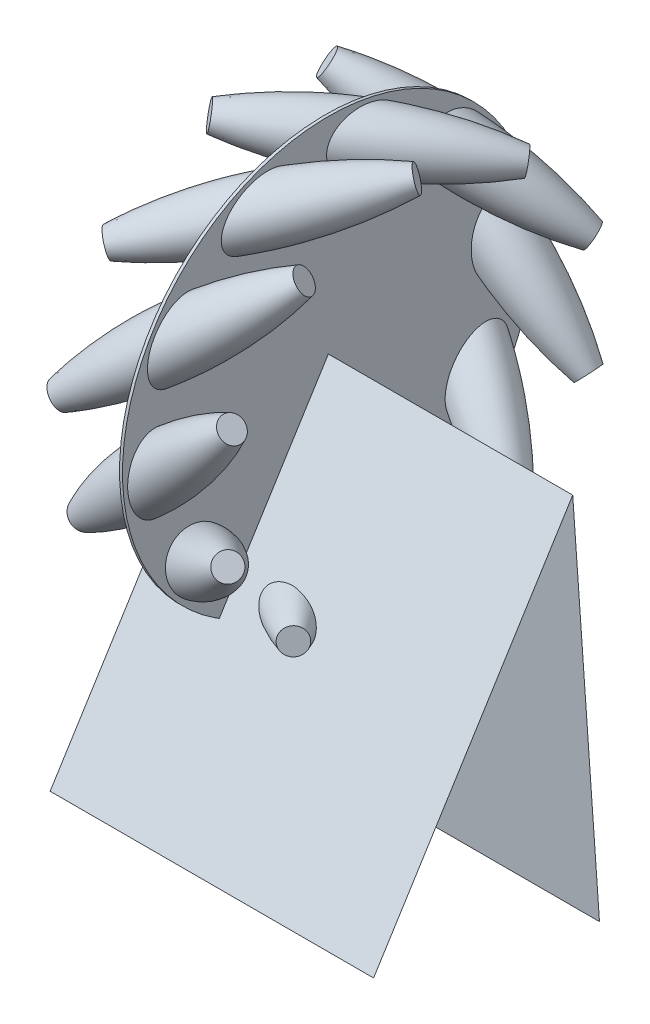
SolidWorks part; units mm, degrees
note: '?' marks a value the reader was unsure of.
ref_plane "前视基准面" through (0, 0, 0) normal (0, 0, 1) x (1, 0, 0)
ref_plane "上视基准面" through (0, 0, 0) normal (0, 1, 0) x (1, 0, 0)
ref_plane "右视基准面" through (0, 0, 0) normal (1, 0, 0) x (0, 0, -1)
sketch "草图1" plane through (0, 0, 0) normal (1, 0, 0) x (0, 0, -1)
  line L0 (0, 0) -> (0, 70) construction
  line L1 (0, 0) -> (35, 60.6218) construction
  line L2 (0, 0) -> (60.6218, 35) construction
  line L3 (0, 0) -> (70, 0) construction
  line L4 (0, 0) -> (60.6218, -35) construction
  line L5 (0, 0) -> (35, -60.6218) construction
  line L6 (0, 0) -> (0, -70) construction
  line L7 (0, 0) -> (-35, -60.6218) construction
  line L8 (0, 0) -> (-60.6218, -35) construction
  line L9 (0, 0) -> (-70, 0) construction
  line L10 (0, 0) -> (-60.6218, 35) construction
  line L11 (0, 0) -> (-35, 60.6218) construction
  line L12 (0, 0) -> (65.7785, -23.9414) construction
  line L13 (56.2917, 32.5) -> (60.6218, -22.0645)
  circle A0 centre (0, 0) radius 65
  circle A1 centre (0, 0) radius 70
  point P18 (0, 0)
  dimension "D1" = 12
  dimension "D2" = 50
ref_plane "基准面1" through (0, 4.6426, -58.5024) normal (0, -0.0791, 0.9969) x (0, -0.9969, -0.0791)
sketch "草图2" plane through (0, 4.6426, -58.5024) normal (0, -0.0791, 0.9969) x (0, -0.9969, -0.0791)
  line L0 (26.7911, 0) -> (26.7911, 54.7361) construction
  line L1 (26.7911, 54.7361) -> (-27.945, 0)
  dimension "D1" = 45
ref_axis "基准轴1" through (0, 0, 0) along (1, 0, 0)
sketch3d "3D草图1"
  line L0 (0, 0, 0) -> (101.2389, 0, 0) construction
  line L1 (27.368, 5.2177, -58.4567) -> (26.3985, 0, 0) construction
  line L2 (54.7361, -22.0645, -60.6218) -> (0, 32.5, -56.2917) construction
ref_plane "基准面5" through (13.1947, 13.1258, 1.3904) normal (0.707, 0.7033, 0.0745) x (0.0528, 0.0525, -0.9972)
sketch3d "3D草图3"
  line L1 (0, 0, 70) -> (19.022, 0, 70) construction
  line L3 (0, 0, -70) -> (33.775, 0, -70) construction
  point P0 (0, 0, 70)
sketch "特征线" plane through (13.1947, 13.1258, 1.3904) normal (0.707, 0.7033, 0.0745) x (0.0528, 0.0525, -0.9972)
  line L3 (60.0139, -15.6023) -> (1.3943, -18.6176) construction
  ellipse E0 centre (1.3943, -18.6176) end of major axis (6.479, -117.4669) minor radius 68.5
  dimension "D1" = 137
  dimension "D2" = 197.96
sketch "草图5" plane through (13.1947, 13.1258, 1.3904) normal (0.707, 0.7033, 0.0745) x (0.0528, 0.0525, -0.9972)
  line L0 (62.185, -54.2456) -> (57.8428, 23.041) construction
  line L1 (62.185, -54.2456) -> (57.8428, 23.041)
  line L2 (57.8428, 23.041) -> (62.3614, 23.2949)
  line L3 (62.185, -54.2456) -> (66.3501, -54.0116)
  ellipse E0 centre (1.3943, -18.6176) end of major axis (6.479, -117.4669) minor radius 68.5 construction
  ellipse E1 centre (1.3943, -18.6176) end of major axis (6.479, -117.4669) minor radius 68.5 (66.3501, -54.0116) -> (62.3614, 23.2949) ccw
revolve "旋转1" add sketch "草图5" angle 360 about L1
ref_plane "基准面6" through (26.3985, 0, 0) normal (1, 0, 0) x (0, 0, -1)
sketch "草图6" plane through (26.3985, 0, 0) normal (1, 0, 0) x (0, 0, -1)
  circle A0 centre (0, 0) radius 70 construction
  circle A1 centre (0, 0) radius 70
extrude "凸台-拉伸1" add sketch "草图6" along normal mid plane 1
pattern_circular "阵列(圆周)2" count 10 over 360 about axis through (0, 0, 0) along (1, 0, 0) of "旋转1"
other "Configuration Table"
sketch "草图7" plane through (0, 0, 0) normal (0, 0, 1) x (1, 0, 0)
  line L0 (67.1878, 30.2938) -> (61.1961, 17.876)
  line L2 (61.1961, 17.876) -> (54.1338, 17.876)
  line L3 (67.1878, 30.2938) -> (67.1878, 42.7765)
  line L4 (67.1878, 42.7765) -> (61.7777, 62.7388)
sketch "草图8" plane through (0, 0, 0) normal (1, 0, 0) x (0, 0, -1)
  line L0 (0, 0) -> (-67.7114, -108.3608)
  line L1 (0, 0) -> (9.1025, -130.1715)
  line L2 (0, 0) -> (0, -143.1755) construction
  line L3 (0, 46.9609) -> (0, -46.9609) construction
  dimension "D1" = 32
  dimension "D2" = 36
surface "曲面-拉伸1" sketch "草图8" parameters "D1"=110
surface "曲面-旋转1" sketch "草图7" parameters "D1"=360
surface "曲面-剪裁1"
sketch "草图9" plane through (0, 0, 0) normal (1, 0, 0) x (0, 0, -1)
sketch "草图10" plane through (0, 0, 0) normal (1, 0, 0) x (0, 0, -1)
  line L0 (4.3764, -62.586) -> (-26.2451, -42.001)
  line L1 (-22.6681, -36.2765) -> (-33.2465, -53.2055) construction
surface "曲面-剪裁2"
sketch "草图11" plane through (0, 0, 0) normal (0, -0.5299, -0.848) x (-1, 0, 0)
  line L0 (-65.3584, -49.5266) -> (-63.5365, -56.2493)
  line L1 (-67.1878, -42.7765) -> (-65.3584, -49.5266) construction
sketch3d "3D草图4"
  line L0 (63.5365, -47.7021, 29.8076) -> (63.5365, -77.1863, -17.3769) construction
  line L1 (63.5365, -55.4008, 17.4871) -> (63.5365, -39.8243, 42.4147) construction
  line L3 (61.7775, -62.5865, -4.3765) -> (67.1878, -42.6723, -2.9839) construction
  spline S0 degree 3 poles (63.5365, -47.7021, 29.8076) (63.5365, -54.1923, 19.4211) (58.7395, -66.0826, 10.8621) (56.9461, -66.1414, -0.8137) knots 0 0 0 0 1 1 1 1
  spline S1 degree 3 poles (61.7777, -62.586, -4.3764) (61.3381, -65.0135, 0.0545) (57.1652, -64.7494, -1.2293) (56.9461, -66.1414, -0.8137) knots 0 0 0 0 1 1 1 1
  spline S2 degree 3 poles (65.3584, -42.0009, 26.2451) (65.3536, -42.2988, 25.8019) (65.3393, -42.8951, 24.915) (65.2976, -43.9396, 23.3614) (65.2271, -45.1382, 21.5781) (65.0791, -46.9382, 18.9008) (64.8188, -49.1854, 15.5577) (64.3959, -51.8656, 11.5709) (63.8703, -54.5502, 7.5768) (63.3791, -56.6855, 4.4009) (62.9764, -58.2883, 2.0166) (62.6989, -59.3451, 0.4446) (62.4065, -60.4141, -1.1456) (62.1087, -61.4646, -2.7082) (61.8902, -62.2091, -3.8159) (61.7775, -62.5865, -4.3771) knots 0 0 0 0 0.043119 0.086313 0.151515 0.216916 0.347383 0.477798 0.606745 0.738719 0.789693 0.841267 0.893485 0.946384 1 1 1 1 construction
ref_axis "基准轴2" through (63.5365, -47.7021, 29.8076) along (0, -0.5299, -0.848)?
sketch "草图12" plane through (40.7636, -15.6241, 37.6505) normal (0.7071, -0.271, 0.6531) x (0.6098, -0.2337, -0.7573)
  line L0 (50.9174, -40.6125) -> (42.5741, -40.6125) construction
  line L1 (46.7457, -36.4409) -> (46.7457, -44.7842) construction
  circle A0 centre (46.7457, -40.6125) radius 4.1716 construction
  point P6 (46.7457, -40.6125)
ref_axis "基准轴3" through (-33.6532, -30.5947, -79.3875) along (0.7071, -0.271, 0.6531)?
sketch "草图14" plane through (40.7636, -15.6241, 37.6505) normal (0.7071, -0.271, 0.6531) x (0.6098, -0.2337, -0.7573)
  line L0 (46.7457, -40.6125) -> (50.5684, -38.9424) construction
  circle A0 centre (46.7457, -40.6125) radius 4.1716 construction
ref_plane "基准面7" through (-4.6874, -53.0917, -16.9569) normal (-0.0838, -0.9492, -0.3032) x (-0.9965, 0.0798, 0.0255)
sketch "草图15" plane through (-4.6874, -53.0917, -16.9569) normal (-0.0838, -0.9492, -0.3032) x (-0.9965, 0.0798, 0.0255)
  line L1 (3.3059, 47.0219) -> (29.4391, 47.0219)
  line L2 (3.3059, 47.0219) -> (3.3059, -2.1925)
  line L3 (3.3059, -2.1925) -> (29.4391, -2.1925)
  line L4 (29.4391, 47.0219) -> (29.4391, -2.1925)
surface "曲面-基准面1" sketch "草图15"
sketch3d "3D草图6"
  spline S0 degree 3 poles (26.8985, -49.734, -36.2009) (39.5069, -54.09, -26.048) (49.9831, -58.8819, -13.9404) (57.6651, -63.8071, -0.6434) knots 0 0 0 0 1 1 1 1 weights 1 0.978937 0.978937 1 only from (25.8631, -52.6021, -36.3032) to (56.9461, -66.1414, -0.8137)
  spline S1 degree 3 poles (51.8071, -65.139, 5.1463) (43.0575, -63.0086, 0.8945) (34.6863, -60.5671, -4.4356) (26.8985, -57.8744, -10.7135) knots 0 0 0 0 1 1 1 1 weights 1 0.991836 0.991836 1
  spline S2 degree 3 poles (51.8071, -65.139, 5.1463) (43.0575, -63.0086, 0.8945) (34.6863, -60.5671, -4.4356) (26.8985, -57.8744, -10.7135) knots 0 0 0 0 1 1 1 1 weights 1 0.991836 0.991836 1
  spline S3 degree 3 poles (25.8631, -52.6021, -36.3032) (38.5646, -56.7725, -26.1884) (49.1485, -61.3827, -14.1041) (56.9461, -66.1414, -0.8137) knots 0 0 0 0 1 1 1 1 weights 1 0.978937 0.978937 1
sketch3d "3D草图7" plane through (0, 0, 0) normal (0, 0, 1) x (1, 0, 0)
other "边界-曲面2"
sketch3d "3D草图8" plane through (0, 0, 0) normal (0, 0, 1) x (1, 0, 0)
sketch "草图17" plane through (0, 0, 0) normal (0, -0.5299, -0.848) x (-1, 0, 0)
  line L0 (-63.5365, -56.2493) -> (-61.7792, -62.7334)
  line L1 (-65.065, -50.6092) -> (-63.5365, -56.2493) construction
sketch3d "3D草图10"
  spline S0 degree 3 poles (61.7792, -53.2009, 33.2436) (57.4966, -60.7318, 18.57) (51.3342, -67.9037, 7.0735) (53.243, -68.3684, 2.2514) knots 0 0 0 0 1 1 1 1
sketch "草图19" plane through (40.7636, -15.6241, 37.6505) normal (0.7071, -0.271, 0.6531) x (0.6098, -0.2337, -0.7573)
sketch "草图20" plane through (0, 0, 0) normal (1, 0, 0) x (0, 0, -1)
  line L0 (0, 0) -> (-33.1676, -53.0793)
  line L1 (0, 0) -> (-67.7114, -108.3608) construction
  point P5 (0, 0)
  point P6 (0, 0)
sketch3d "3D草图11"
  line L0 (110, 0, 0) -> (110, -108.3608, 67.7114) construction
  spline S0 degree 1 poles (0, -53.0793, 33.1676) (110, -54.1804, 33.8557) knots 0 0 1 1
